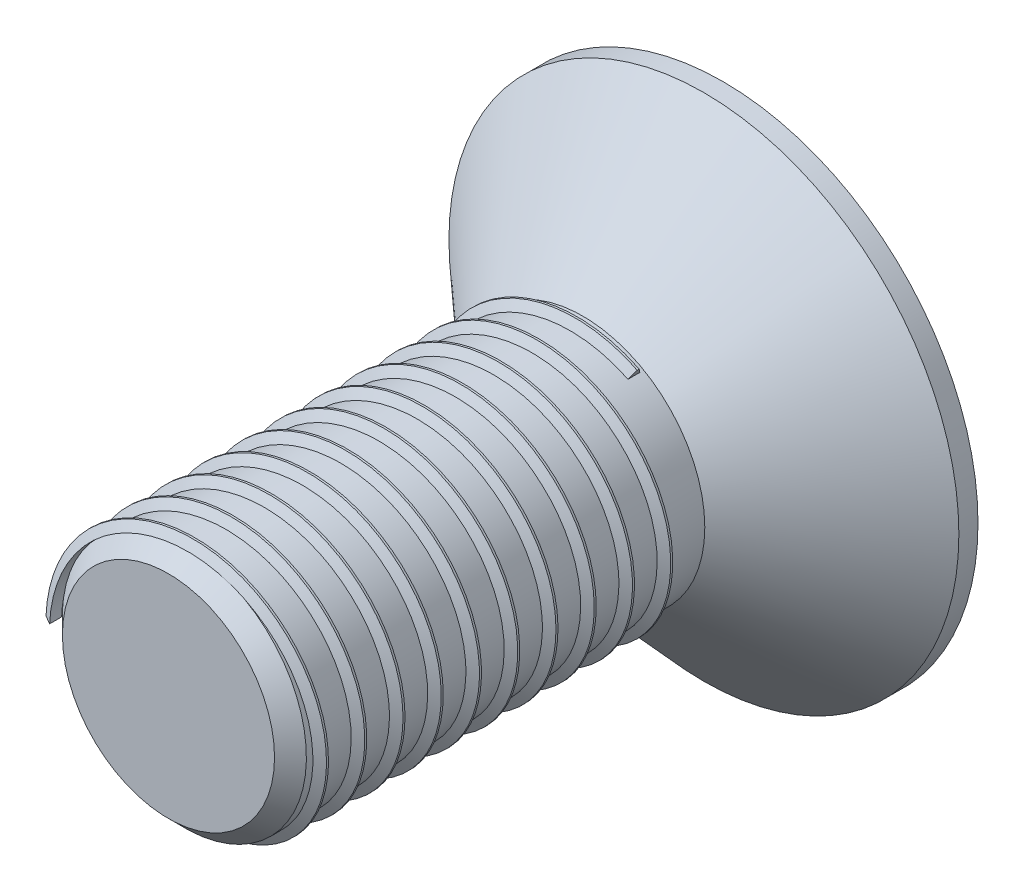
SolidWorks part; units mm, degrees
material "Acero aleado"
ref_plane "Alzado" through (0, 0, 0) normal (0, 0, 1) x (1, 0, 0)
ref_plane "Planta" through (0, 0, 0) normal (0, 1, 0) x (1, 0, 0)
ref_plane "Vista lateral" through (0, 0, 0) normal (1, 0, 0) x (0, 0, -1)
sketch "Croquis1" plane through (0, 0, 0) normal (0, 0, 1) x (1, 0, 0)
  circle A0 centre (0, 0) radius 1.9141
  dimension "D1" = 3.8281
extrude "Saliente-Extruir3" add sketch "Croquis1" along normal blind 6.5 contours A0
sketch "Croquis5" plane through (0, 0, 0) normal (1, 0, 0) x (0, 0, -1)
  line L0 (0, 0) -> (2.2, 0) construction
  line L1 (2.2, 4) -> (2.2, -4) construction
  line L2 (2.2, 4) -> (1.9, 4)
  line L3 (1.9, 4) -> (0, 1.9141)
  line L8 (2.2, 4) -> (2.2, 0)
  line L9 (2.2, 0) -> (0, 0)
  line L10 (0, 0) -> (0, 1.9141)
  point P5 (2.2, 0)
  dimension "D1" = 2.2
  dimension "D2" = 8
  dimension "D3" = 0.3
revolve "Revolución1" add sketch "Croquis5" angle 360 about L9
chamfer "Chaflán1" distance 0.25 angle 45 1 edges at (1.9141, 0, 6.5)
thread "Rosca1" pitch 0.25 method extrude profile "Perfil de rosca1" start angle 0, offset 0.2, length 6.2, pitch 0.6, diameter 3.8281
ref_plane "Plano1" through (-1.9141, 0, 6.45) normal (0, -1, 0) x (-1, 0, 0)
sketch "Perfil de rosca1" plane through (-1.9141, 0, 6.45) normal (0, -1, 0) x (-1, 0, 0)
  line L0 (0, 0) -> (0, 0.25) construction
  line L1 (0, 0) -> (0.1353, 0.0781)
  line L2 (0.1353, 0.0781) -> (0.1353, 0.1094)
  line L3 (0.1353, 0.1094) -> (0, 0.1875)
  line L4 (0.1353, 0.0937) -> (0, 0.0937) construction
  line L11 (0, 0) -> (0, 0.1875)
  point P2 (0, 0)
  dimension "Pitch" = 0.25
  dimension "Profile_Angle" = 60
  dimension "Profile_Land" = 0.0312
  dimension "Profile_Height" = 0.1353
sketch "Croquis16" plane through (0, 0, -2.2) normal (0, 0, -1) x (-1, 0, 0)
  line L1 (1.3, -0.7506) -> (1.3, 0.7506)
  line L2 (1.3, 0.7506) -> (0, 1.5011)
  line L3 (0, 1.5011) -> (-1.3, 0.7506)
  line L4 (-1.3, 0.7506) -> (-1.3, -0.7506)
  line L5 (-1.3, -0.7506) -> (0, -1.5011)
  line L6 (0, -1.5011) -> (1.3, -0.7506)
  circle A0 centre (0, 0) radius 1.3 construction
  dimension "D1" = 2.6
extrude "Cortar-Extruir1" cut sketch "Croquis16" against normal blind 1.5
chamfer "Chaflán2" distance 0.15 angle 45 6 edges at (0.65, -1.1258, -0.7) (1.3, 0, -0.7) (0.65, 1.1258, -0.7) (-0.65, 1.1258, -0.7) (-1.3, 0, -0.7) (-0.65, -1.1258, -0.7)
